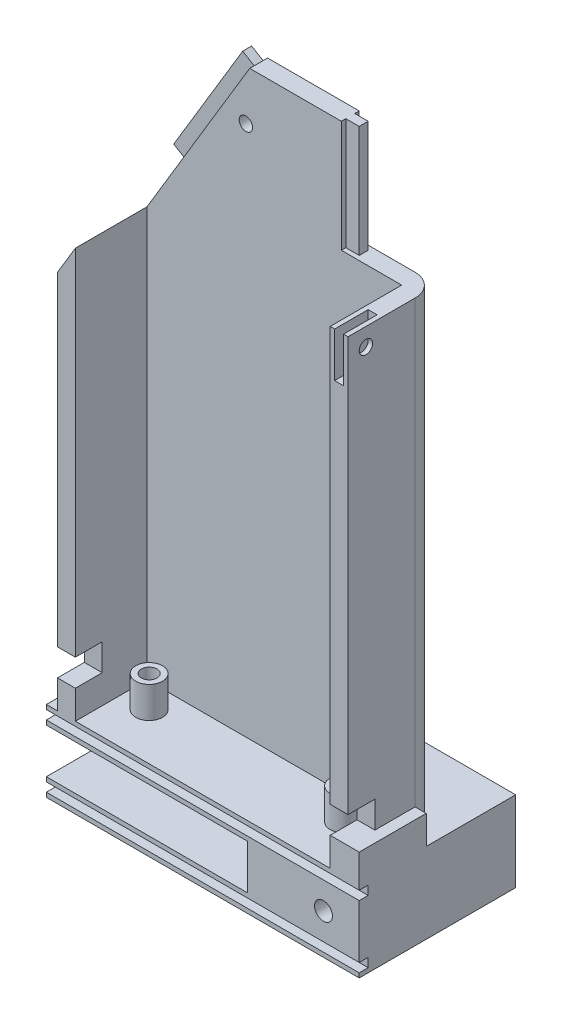
SolidWorks part; units mm, degrees
ref_plane "Front Plane" through (0, 0, 0) normal (0, 0, 1) x (1, 0, 0)
ref_plane "Top Plane" through (0, 0, 0) normal (0, 1, 0) x (1, 0, 0)
ref_plane "Right Plane" through (0, 0, 0) normal (1, 0, 0) x (0, 0, -1)
sketch "Sketch1" plane through (0, 0, 0) normal (0, 1, 0) x (1, 0, 0)
  line L1 (-32.5, -20) -> (32.5, -20)
  line L2 (-32.5, -20) -> (-32.5, 20)
  line L3 (-32.5, 20) -> (32.5, 20)
  line L4 (32.5, -20) -> (32.5, 20)
  line L5 (-32.5, -20) -> (32.5, 20) construction
  line L6 (-32.5, 20) -> (32.5, -20) construction
  point P0 (0, 0)
  dimension "D1" = 65
  dimension "D2" = 40
extrude "Boss-Extrude1" add sketch "Sketch1" along normal blind 130
shell "Shell1" thickness 4 removed face at (0, 0, 0) removed face at (0, 130, 0)
fillet "Fillet1" radius 5 4 edges at (32.5, 65, -20) (32.5, 65, 20) (-32.5, 65, -20) (-32.5, 65, 20)
sketch "Sketch2" plane through (0, 0, 0) normal (0, 0, 1) x (1, 0, 0)
  line L0 (-5.5, 130) -> (-32.5, 85)
  line L1 (28.5, 130) -> (-28.5, 130) construction
  line L2 (-32.5, 130) -> (-32.5, 0) construction
  line L3 (-32.5, 85) -> (-32.5, 130)
  line L4 (-32.5, 130) -> (-5.5, 130)
  dimension "D1" = 5.5
  dimension "D2" = 85
extrude "Cut-Extrude1" cut sketch "Sketch2" against normal through all both and the other way through all
sketch "Sketch3" plane through (0, 0, 0) normal (0, 0, 1) x (1, 0, 0)
  line L1 (32.5, 130) -> (15, 130)
  line L2 (32.5, 130) -> (32.5, 105)
  line L3 (32.5, 105) -> (15, 105)
  line L4 (15, 130) -> (15, 105)
  dimension "D1" = 25
  dimension "D2" = 17.5
extrude "Cut-Extrude2" cut sketch "Sketch3" against normal through all both and the other way through all
sketch "Sketch5" plane through (15, 0, 0) normal (1, 0, 0) x (0, 0, -1)
  line L0 (-18, 130) -> (-18, 105) construction
  line L1 (-16, 130) -> (-20, 130) construction
  line L2 (-16, 105) -> (-20, 105) construction
  line L4 (-19, 130) -> (-17, 130)
  line L5 (-19, 130) -> (-19, 105)
  line L6 (-19, 105) -> (-17, 105)
  line L7 (-17, 130) -> (-17, 105)
  dimension "D1" = 2
extrude "Boss-Extrude2" add sketch "Sketch5" along normal blind 3
mirror "Mirror1" about plane through (0, 0, 0) normal (0, 0, 1) of "Boss-Extrude2"
sketch "Sketch6" plane through (-61.3971, 36.8382, 0) normal (-0.8575, 0.5145, 0) x (0, 0, 1)
  line L0 (-18, 108.6444) -> (-18, 78.6444) construction
  line L1 (-20, 108.6444) -> (-16, 108.6444) construction
  line L3 (-19, 108.6444) -> (-17, 108.6444)
  line L4 (-19, 108.6444) -> (-19, 78.6444)
  line L5 (-19, 78.6444) -> (-17, 78.6444)
  line L6 (-17, 108.6444) -> (-17, 78.6444)
  dimension "D1" = 30
  dimension "D2" = 2
extrude "Boss-Extrude3" add sketch "Sketch6" along normal blind 3
mirror "Mirror2" about plane through (0, 0, 0) normal (0, 0, 1) of "Boss-Extrude3"
sketch "Sketch8" plane through (0, 0, 0) normal (0, 1, 0) x (1, 0, 0)
  line L1 (-35, -35) -> (35, -35)
  line L2 (-35, -35) -> (-35, 35)
  line L3 (-35, 35) -> (35, 35)
  line L4 (35, -35) -> (35, 35)
  line L5 (-35, -35) -> (35, 35) construction
  line L6 (-35, 35) -> (35, -35) construction
  point P0 (0, 0)
  dimension "D1" = 70
  dimension "D2" = 70
extrude "Boss-Extrude4" add sketch "Sketch8" against normal blind 18
sketch "Sketch10" plane through (-35, 0, 0) normal (-1, 0, 0) x (0, 0, 1)
  line L0 (-35, -9) -> (35, -9) construction
  line L1 (-30, -14) -> (30, -14)
  line L2 (-30, -14) -> (-30, -4)
  line L3 (-30, -4) -> (30, -4)
  line L4 (30, -14) -> (30, -4)
  line L5 (-30, -14) -> (30, -4) construction
  line L6 (-30, -4) -> (30, -14) construction
  line L7 (-35, -18) -> (-35, 0) construction
  line L8 (35, -18) -> (35, 0) construction
  line L9 (0, 0) -> (0, -18) construction
  line L10 (-35, -18) -> (35, -18) construction
  point P0 (0, -9)
  dimension "D1" = 60
  dimension "D2" = 10
extrude "Cut-Extrude4" cut sketch "Sketch10" against normal blind 45
sketch "Sketch23" plane through (0, 105, 0) normal (0, 1, 0) x (1, 0, 0)
  line L0 (0, 0) -> (32.5, 0) construction
  line L1 (29.5, 7.5) -> (31.5, 7.5)
  line L2 (29.5, 7.5) -> (29.5, -7.5)
  line L3 (29.5, -7.5) -> (31.5, -7.5)
  line L4 (31.5, 7.5) -> (31.5, -7.5)
  line L5 (32.5, 15) -> (32.5, -15) construction
  line L6 (28.5, 16) -> (28.5, -16) construction
  line L8 (30.5, 14.75) -> (30.5, -14.75) construction
  dimension "D1" = 2
  dimension "D2" = 15
extrude "Cut-Extrude10" cut sketch "Sketch23" against normal blind 10
sketch "Sketch27" plane through (0, 0, 0) normal (0, 1, 0) x (1, 0, 0)
  line L0 (35, -35) -> (35, 35) construction
  line L1 (-35, -35) -> (35, -35)
  line L2 (-35, -35) -> (-35, 0)
  line L3 (-35, 0) -> (35, 0)
  line L4 (35, -35) -> (35, 0)
extrude "Cut-Extrude12" cut sketch "Sketch27" against normal through all both and the other way through all
sketch "Sketch29" plane through (0, 0, 0) normal (0, 0, 1) x (1, 0, 0)
  line L0 (-35, -2) -> (35, -2) construction
  line L1 (-35, -4) -> (-35, 0) construction
  line L2 (35, -18) -> (35, 0) construction
  line L3 (-35, -1) -> (35, -1)
  line L4 (-35, -1) -> (-35, -3)
  line L5 (-35, -3) -> (35, -3)
  line L6 (35, -1) -> (35, -3)
  dimension "D1" = 2
extrude "Cut-Extrude13" cut sketch "Sketch29" against normal blind 2
sketch "Sketch30" plane through (0, 0, 0) normal (0, 0, 1) x (1, 0, 0)
  line L0 (-35, -16) -> (35, -16) construction
  line L1 (-35, -18) -> (-35, -14) construction
  line L2 (35, -18) -> (35, -3) construction
  line L4 (-35, -15) -> (35, -15)
  line L5 (-35, -15) -> (-35, -17)
  line L6 (-35, -17) -> (35, -17)
  line L7 (35, -15) -> (35, -17)
  dimension "D1" = 2
extrude "Cut-Extrude14" cut sketch "Sketch30" against normal blind 2
sketch "Sketch31" plane through (0, 0, 0) normal (0, 0, 1) x (1, 0, 0)
  line L0 (35, -15) -> (35, -3) construction
  line L1 (35, -18) -> (-35, -18) construction
  circle A0 centre (27, -9) radius 2
  dimension "D1" = 4
  dimension "D2" = 8
  dimension "D3" = 9
extrude "Cut-Extrude15" cut sketch "Sketch31" against normal through all both and the other way through all
sketch "Sketch33" plane through (0, 0, -35) normal (0, 0, -1) x (-1, 0, 0)
  circle A0 centre (-27, -9) radius 4
  dimension "D1" = 8
extrude "Cut-Extrude16" cut sketch "Sketch33" against normal blind 15
sketch "Sketch34" plane through (0, 0, 0) normal (0, 1, 0) x (1, 0, 0)
  line L1 (35, 0) -> (35, 35) construction
  line L2 (35, 35) -> (-35, 35) construction
  circle A0 centre (0, 25.5) radius 1.5
  dimension "D2" = 3
  dimension "D1" = 9.5
  dimension "D3" = 35
extrude "Cut-Extrude17" cut sketch "Sketch34" against normal through all both and the other way through all
sketch "Sketch35" plane through (0, -18, 0) normal (0, -1, 0) x (-1, 0, 0)
  circle A0 centre (0, 25.5) radius 4
  dimension "D1" = 8
extrude "Cut-Extrude18" cut sketch "Sketch35" against normal blind 3
sketch "Sketch39" plane through (0, 0, 0) normal (0, 1, 0) x (1, 0, 0)
  line L0 (-28.5, 0) -> (28.5, 0) construction
  line L2 (28.5, 16) -> (28.5, 0) construction
  circle A0 centre (21, 10.5) radius 3
  dimension "D1" = 6
  dimension "D2" = 10.5
  dimension "D3" = 7.5
extrude "Boss-Extrude7" add sketch "Sketch39" along normal blind 7
sketch "Sketch40" plane through (0, 7, 0) normal (0, 1, 0) x (1, 0, 0)
  circle A0 centre (21, 10.5) radius 1.75
  dimension "D1" = 3.5
extrude "Cut-Extrude20" cut sketch "Sketch40" against normal blind 4
pattern_linear "LPattern4" count 2 spacing 43.5 along (-1, 0, 0) of "Boss-Extrude7", "Cut-Extrude20"
sketch "Sketch41" plane through (32.5, 0, 0) normal (1, 0, 0) x (0, 0, -1)
  line L0 (0, 105) -> (0, 0) construction
  line L1 (6, 6.4) -> (0, 6.4)
  line L2 (6, 6.4) -> (6, 12.4)
  line L3 (6, 12.4) -> (0, 12.4)
  line L4 (0, 6.4) -> (0, 12.4)
  line L5 (0, 0) -> (15, 0) construction
  dimension "D1" = 6.4
  dimension "D2" = 6
  dimension "D3" = 6
extrude "Cut-Extrude21" cut sketch "Sketch41" against normal through all both and the other way through all
sketch "Sketch42" plane through (32.5, 0, 0) normal (1, 0, 0) x (0, 0, -1)
  line L1 (0, 6.4) -> (15, 6.4)
  line L2 (0, 6.4) -> (0, 0)
  line L3 (0, 0) -> (15, 0)
  line L4 (15, 6.4) -> (15, 0)
extrude "Boss-Extrude10" add sketch "Sketch42" along normal up to surface (2.5 mm away) up to face at (35, -9, -6.5)
sketch "Sketch43" plane through (32.5, 0, 0) normal (1, 0, 0) x (0, 0, -1)
  line L0 (0, 105) -> (0, 12.4) construction
  line L1 (15, 105) -> (0, 105) construction
  circle A0 centre (4, 101) radius 1.5
  dimension "D3" = 3
  dimension "D1" = 4
  dimension "D2" = 4
extrude "Cut-Extrude22" cut sketch "Sketch43" against normal blind 10 and the other way through all
sketch "Sketch45" plane through (0, 0, -35) normal (0, 0, -1) x (-1, 0, 0)
  line L0 (35, -9) -> (-35, -9) construction
  line L1 (35, -18) -> (35, 0) construction
  line L2 (-35, -18) -> (-35, 0) construction
  line L4 (29.5, -7) -> (25, -7)
  line L5 (29.5, -7) -> (29.5, -11)
  line L6 (29.5, -11) -> (25, -11)
  line L7 (25, -7) -> (25, -11)
  dimension "D1" = 5.5
  dimension "D2" = 4.5
  dimension "D3" = 4
extrude "Boss-Extrude11" add sketch "Sketch45" along normal blind 3
sketch "Sketch46" plane through (0, -7, 0) normal (0, 1, 0) x (1, 0, 0)
  line L0 (-29.5, 35) -> (-25, 38)
  line L1 (-25, 38) -> (-29.5, 38)
  line L2 (-29.5, 38) -> (-29.5, 35)
extrude "Cut-Extrude23" cut sketch "Sketch46" against normal through all
fillet "Fillet2" radius 1 1 edges at (-25, -9, -38)
sketch "Sketch49" plane through (0, 0, -20) normal (0, 0, -1) x (-1, 0, 0)
  line L0 (6.3575, 118.8526) -> (10.645, 121.4251) construction
  line L1 (5.5, 130) -> (20.9349, 104.2752) construction
  circle A0 centre (6.3575, 118.8526) radius 1.5
  dimension "D1" = 3
  dimension "D4" = 5
  dimension "D2" = 5
  dimension "D3" = 10
extrude "Cut-Extrude24" cut sketch "Sketch49" against normal through all both and the other way through all
